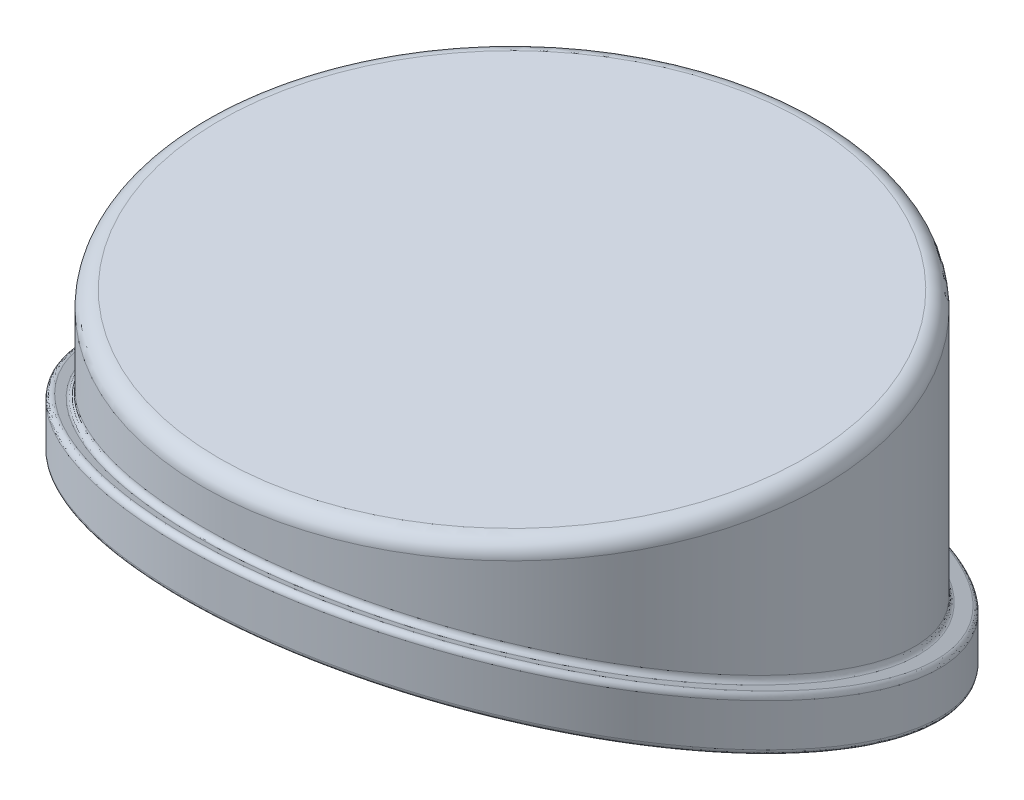
SolidWorks part; units mm, degrees
ref_plane "Front Plane" through (0, 0, 0) normal (0, 0, 1) x (1, 0, 0)
ref_plane "Top Plane" through (0, 0, 0) normal (0, 1, 0) x (1, 0, 0)
ref_plane "Right Plane" through (0, 0, 0) normal (1, 0, 0) x (0, 0, -1)
sketch "Sketch3" plane through (0, 0, 0) normal (0, 1, 0) x (1, 0, 0)
  circle A0 centre (0, 0) radius 40
  dimension "D1" = 80
extrude "Boss-Extrude3" add sketch "Sketch3" along normal blind 12.5781 contours A0
sketch "Sketch6" plane through (0, 0, 0) normal (1, 0, 0) x (0, 0, -1)
  line L0 (-40, 0) -> (40, -32)
  line L1 (-40, 0) -> (40, 0) construction
  line L2 (40, -32) -> (40, 0)
  line L3 (40, 0) -> (-40, 0)
  dimension "D1" = 21.801
extrude "Boss-Extrude4" add sketch "Sketch6" along normal up to surface and the other way up to surface up to face at (0, 12.5781, 40) other way up to face at (0, 12.5781, 40)
sketch "Sketch8" plane through (0, 12.5781, 0) normal (0, 1, 0) x (1, 0, 0)
  circle A0 centre (0, 0) radius 37.5
  circle A1 centre (0, 0) radius 40
  circle A2 centre (0, 0) radius 40 construction
  dimension "D1" = 75
extrude "Cut-Extrude3" cut sketch "Sketch8" against normal offset from surface (7.1159 mm away) 6 up to face at (0, -32, -40)
fillet "Fillet1" radius 0.6 3 edges at (0, -32, -40) (0, 6.4622, 40) (0, 5.4622, 37.5)
fillet "Fillet2" radius 2 1 edges at (0, 12.5781, 37.5)
